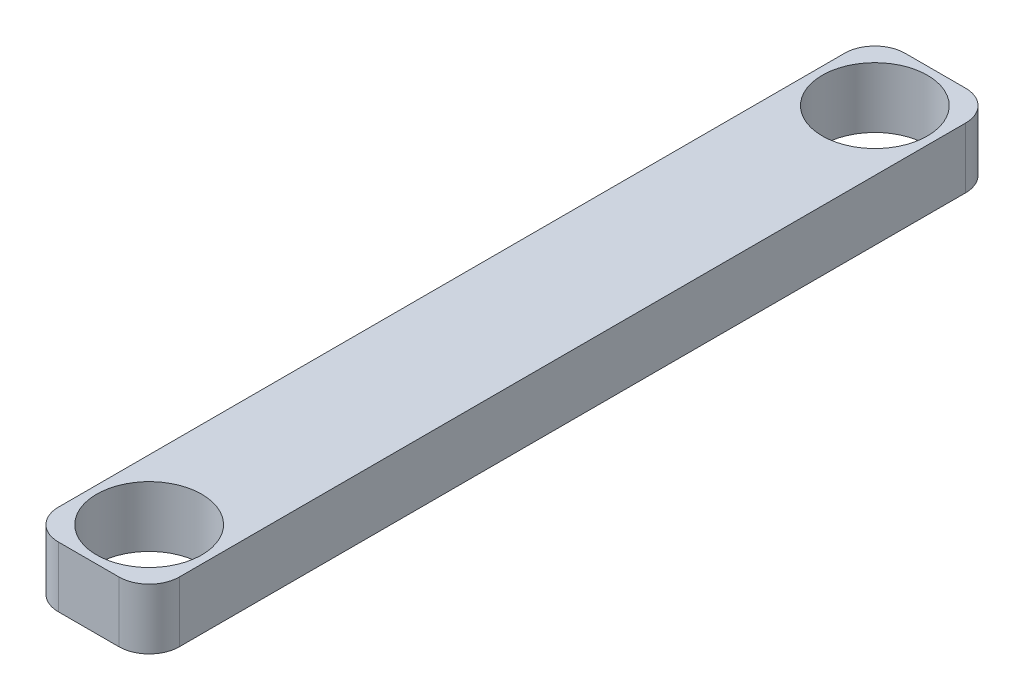
SolidWorks part; units mm, degrees
ref_plane "Front Plane" through (0, 0, 0) normal (0, 0, 1) x (1, 0, 0)
ref_plane "Top Plane" through (0, 0, 0) normal (0, 1, 0) x (1, 0, 0)
ref_plane "Right Plane" through (0, 0, 0) normal (1, 0, 0) x (0, 0, -1)
sketch "Sketch1" plane through (0, 0, 0) normal (0, 1, 0) x (1, 0, 0)
  line L1 (-12.7, -88.9) -> (12.7, -88.9)
  line L2 (-12.7, -88.9) -> (-12.7, 88.9)
  line L3 (-12.7, 88.9) -> (12.7, 88.9)
  line L4 (12.7, -88.9) -> (12.7, 88.9)
  line L5 (-12.7, -88.9) -> (12.7, 88.9) construction
  line L6 (-12.7, 88.9) -> (12.7, -88.9) construction
  point P0 (0, 0)
  dimension "D1" = 25.4
  dimension "D2" = 177.8
extrude "Boss-Extrude1" add sketch "Sketch1" along normal mid plane 12.7
fillet "Fillet1" radius 6.35 4 edges at (12.7, 0, -88.9) (-12.7, 0, -88.9) (12.7, 0, 88.9) (-12.7, 0, 88.9)
sketch "Sketch2" plane through (0, 6.35, 0) normal (0, 1, 0) x (1, 0, 0)
  line L0 (0, 76.2) -> (0, 88.9) construction
  line L1 (6.35, 88.9) -> (-6.35, 88.9) construction
  circle A0 centre (0, 76.2) radius 11.05
  dimension "D2" = 22.1
  dimension "D1" = 12.7
extrude "Cut-Extrude1" cut sketch "Sketch2" against normal through all
mirror "Mirror2" about plane through (0, 0, 0) normal (0, 0, 1) of "Cut-Extrude1"
